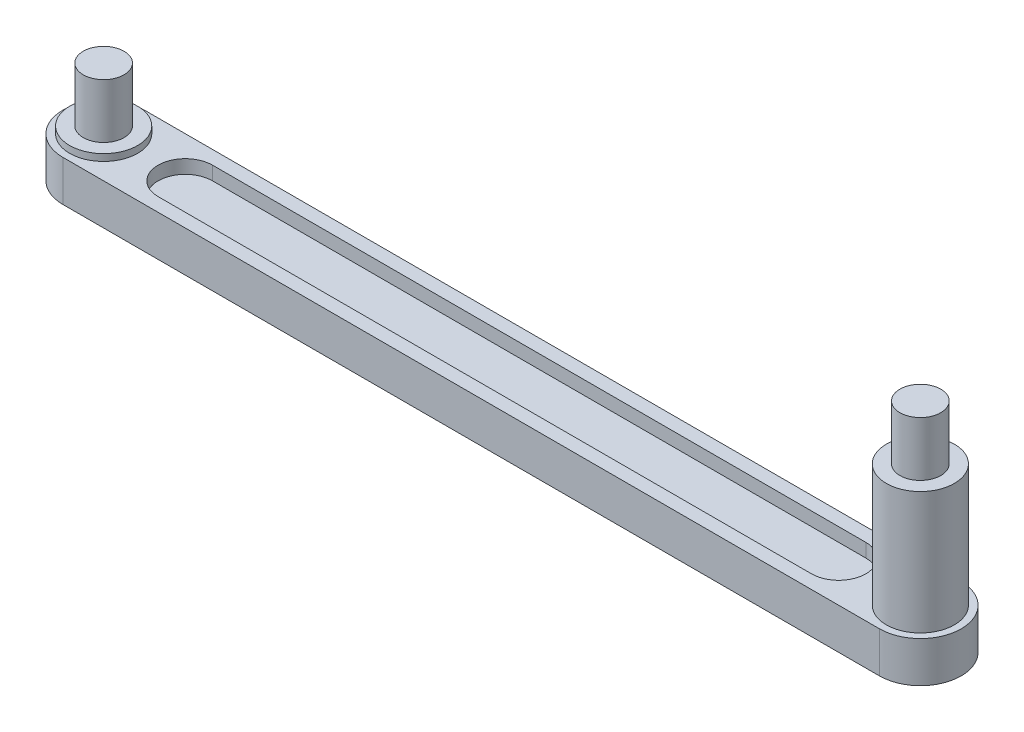
SolidWorks part; units mm, degrees
material "ABS"
ref_plane "Спереди" through (0, 0, 0) normal (0, 0, 1) x (1, 0, 0)
ref_plane "Сверху" through (0, 0, 0) normal (0, 1, 0) x (1, 0, 0)
ref_plane "Справа" through (0, 0, 0) normal (1, 0, 0) x (0, 0, -1)
sketch "Эскиз1" plane through (0, 0, 0) normal (0, 1, 0) x (1, 0, 0)
  line L0 (30, 0) -> (-30, 0) construction
  line L1 (30, -3) -> (-30, -3)
  line L2 (30, 3) -> (-30, 3)
  arc A0 (30, -3) -> (30, 3) centre (30, 0) ccw
  arc A1 (-30, 3) -> (-30, -3) centre (-30, 0) ccw
  circle A2 centre (-30, 0) radius 2.5 construction
  point P2 (0, 0)
  dimension "D2" = 5
  dimension "D3" = 0.5
  dimension "D1" = 60
extrude "Бобышка-Вытянуть1" add sketch "Эскиз1" along normal blind 3
sketch "Эскиз2" plane through (0, 3, 0) normal (0, 1, 0) x (1, 0, 0)
  circle A0 centre (-30, 0) radius 2.5
  circle A1 centre (30, 0) radius 2.5
  arc M1 (30, -3) -> (30, 3) centre (30, 0) ccw
  arc M3 (-30, 3) -> (-30, -3) centre (-30, 0) ccw
extrude "Бобышка-Вытянуть2" add sketch "Эскиз2" along normal blind 0.5 contours A0 M3 region at (-30, 3, 0)
sketch "Эскиз3" plane through (0, 3, 0) normal (0, 1, 0) x (1, 0, 0)
  circle A0 centre (-30, 0) radius 1.5
  circle A1 centre (30, 0) radius 1.5
  dimension "D2" = 3
extrude "Бобышка-Вытянуть3" add sketch "Эскиз3" along normal offset from surface (4.5 mm away) 4 contours A0 region at (-30, 3, 0) up to face at (-30, 3.5, 2.5) offset beyond the face yes
extrude "Бобышка-Вытянуть4" add sketch "Эскиз2<3>" along normal blind 9 contours A1 M1 region at (30, 3, 0)
sketch "Эскиз2<3>" plane through (0, 3, 0) normal (0, 1, 0) x (1, 0, 0) same geometry as "Эскиз2"
extrude "Бобышка-Вытянуть5" add sketch "Эскиз3<3>" along normal offset from surface (13 mm away) 4 contours A1 region at (30, 3, 0) up to face at (30, 12, 2.5) offset beyond the face yes
sketch "Эскиз3<3>" plane through (0, 3, 0) normal (0, 1, 0) x (1, 0, 0) same geometry as "Эскиз3"
sketch "Эскиз4" plane through (0, 3, 0) normal (0, 1, 0) x (1, 0, 0)
  line L0 (24, 0) -> (-24, 0) construction
  line L1 (24, -2) -> (-24, -2)
  line L2 (24, 2) -> (-24, 2)
  line L3 (-24, 2) -> (-24, 3) construction
  line L4 (30, 3) -> (-30, 3) construction
  line L6 (-26, 0) -> (-27, 0) construction
  arc A0 (24, -2) -> (24, 2) centre (24, 0) ccw
  arc A1 (-24, 2) -> (-24, -2) centre (-24, 0) ccw
  arc A2 (-30, 3) -> (-30, -3) centre (-30, 0) ccw construction
  point P2 (0, 0)
  dimension "D1" = 1
extrude "Вырез-Вытянуть1" cut sketch "Эскиз4" against normal offset from surface (1 mm away) 2 up to face at (0, 0, 0)
